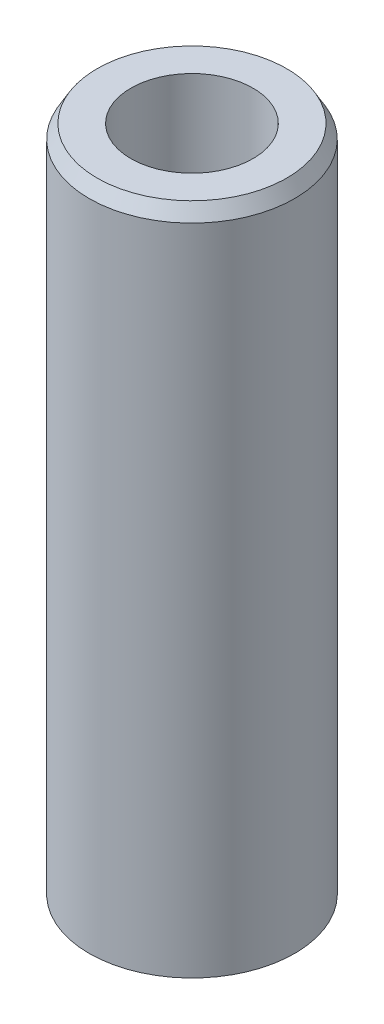
SolidWorks part; units mm, degrees
ref_plane "Front Plane" through (0, 0, 0) normal (0, 0, 1) x (1, 0, 0)
ref_plane "Top Plane" through (0, 0, 0) normal (0, 1, 0) x (1, 0, 0)
ref_plane "Right Plane" through (0, 0, 0) normal (1, 0, 0) x (0, 0, -1)
sketch "Sketch1" plane through (0, 0, 0) normal (0, 1, 0) x (1, 0, 0)
  circle A0 centre (0, 0) radius 17.5
  dimension "SHAFT_OD" = 35
extrude "Boss-Extrude1" add sketch "Sketch1" along normal blind 115.0212
sketch "Sketch2" plane through (0, 0, 0) normal (0, 1, 0) x (1, 0, 0)
  circle A0 centre (0, 0) radius 10.4033
  dimension "BORE_D" = 20.8065
extrude "Cut-Extrude1" cut sketch "Sketch2" along normal through all
chamfer "Chamfer1" distance 2.3413 angle 30 2 edges at (0, 115.0212, 17.5) (0, 0, 17.5) first distance on face at (0, 115.0212, 17.5) first distance on face at (0, 0, 10.4033)
